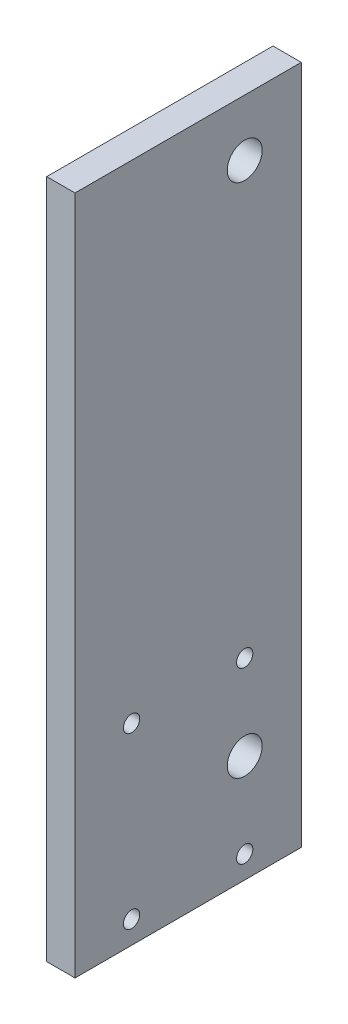
SolidWorks part; units mm, degrees
material "6061-T6 (SS)"
ref_plane "Front" through (0, 0, 0) normal (0, 0, 1) x (1, 0, 0)
ref_plane "Top" through (0, 0, 0) normal (0, 1, 0) x (1, 0, 0)
ref_plane "Right" through (0, 0, 0) normal (1, 0, 0) x (0, 0, -1)
ref_axis "side-side" through (80.9, 0, 0) along (-1, 0, 0)
ref_axis "up-down" through (0, 50, 0) along (0, -1, 0)
ref_axis "front-back" through (0, 0, -80.9) along (0, 0, 1)
sketch "Sketch1" plane through (0, 0, 0) normal (1, 0, 0) x (0, 0, -1)
  line L1 (12.7, 12.7) -> (-38.1, 12.7)
  line L2 (12.7, 12.7) -> (12.7, -139.954)
  line L3 (12.7, -139.954) -> (-38.1, -139.954)
  line L4 (-38.1, 12.7) -> (-38.1, -139.954)
  line L5 (0, -96.774) -> (-25.4, -96.774) construction
  line L6 (0, -96.774) -> (0, -134.874) construction
  line L7 (0, -134.874) -> (-25.4, -134.874) construction
  line L8 (-25.4, -96.774) -> (-25.4, -134.874) construction
  circle A0 centre (0, 0) radius 3.925
  circle A1 centre (0, -115.824) radius 3.925
  circle A2 centre (0, -96.774) radius 1.905 construction
  circle A3 centre (0, -134.874) radius 1.905 construction
  point P15 (0, -132.1562)
  point P16 (0, 0)
  dimension "D1" = 7.85
  dimension "D3" = 12.7
  dimension "D4" = 12.7
  dimension "D6" = 38.1
  dimension "D7" = 3.81
  dimension "D8" = 12.7
  dimension "D2" = 50.8
  dimension "D5" = 128.524
  dimension "D9" = 5.08
extrude "Boss-Extrude1" add sketch "Sketch1" along normal mid plane 6.35
hole_wizard "#6 Clearance Hole1" positions "Sketch2" profile "Sketch3" hole size "#6" standard "ANSI Inch" end condition through all
sketch "Sketch2" plane through (-3.175, 0, 0) normal (-1, 0, 0) x (0, 0, 1)
  point P0 (0, -96.774)
  point P3 (25.4, -96.774)
  point P6 (25.4, -134.874)
  point P9 (0, -134.874)
sketch "Sketch3" plane through (-3.175, -96.774, 0) normal (0, 1, 0) x (0, 0, 1)
  line L0 (0, 0) -> (0, 6.35)
  line L1 (0, 6.35) -> (1.8288, 6.35)
  line L2 (1.8288, 6.35) -> (1.8288, 0)
  line L5 (1.8288, 0) -> (0, 0)
  line L11 (0, -6.35) -> (0, 107.95) construction
  dimension "Thru Hole Dia." = 3.6576
  dimension "Thru Hole Depth" = 6.35
